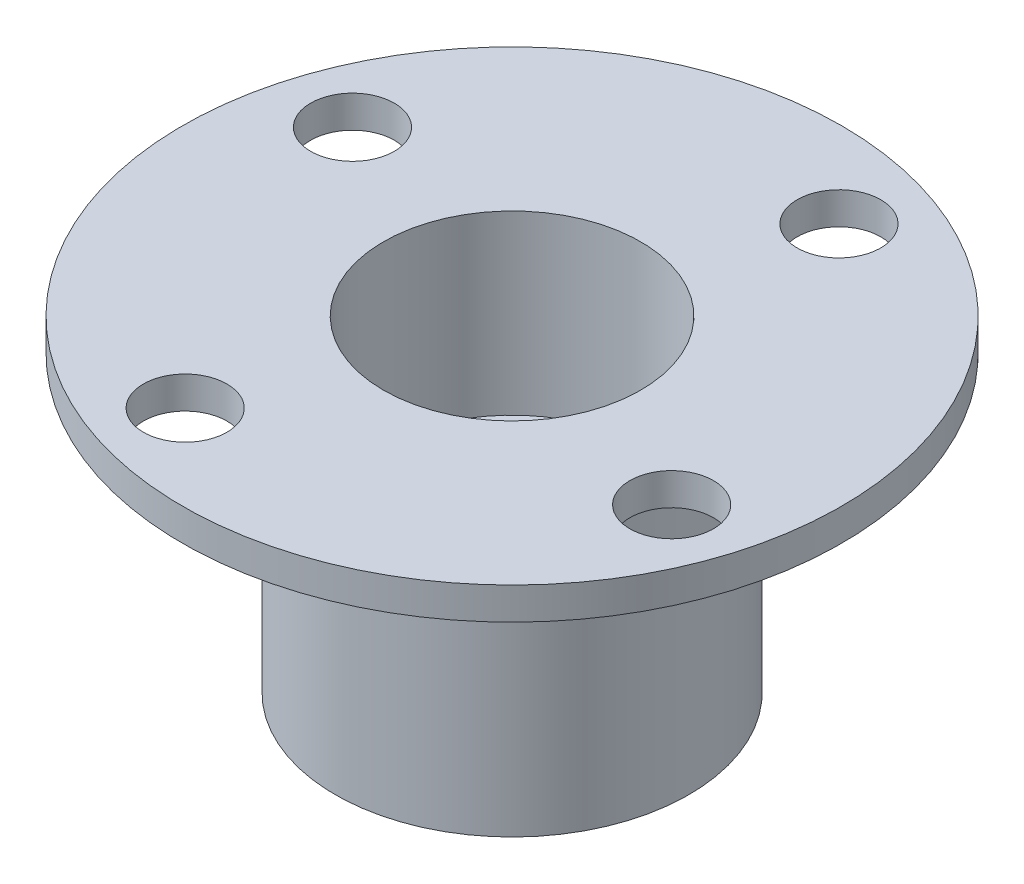
SolidWorks part; units mm, degrees
material "ABS"
ref_plane "Plan de face" through (0, 0, 0) normal (0, 0, 1) x (1, 0, 0)
ref_plane "Plan de dessus" through (0, 0, 0) normal (0, 1, 0) x (1, 0, 0)
ref_plane "Plan de droite" through (0, 0, 0) normal (1, 0, 0) x (0, 0, -1)
sketch "Esquisse1" plane through (0, -38.6013, 0) normal (0, -1, 0) x (1, 0, 0)
  circle A0 centre (14.0172, 17.25) radius 10.25
  arc A1 (9.5205, 8.039) -> (18.514, 26.461) centre (14.0172, 17.25) ccw construction
  dimension "D1" = 20.5
  dimension "D2" = 0
extrude "Boss.-Extru.1" add sketch "Esquisse1" along normal blind 1
hole_wizard "Dégagement M21" positions "Esquisse3" profile "Esquisse4" hole size "M2" standard "Ansi Metric" end condition up to next
sketch "Esquisse3" plane through (0, -39.6013, 0) normal (0, -1, 0) x (-1, 0, 0)
  circle A0 centre (-14.0172, -17.25) radius 8 construction
  point P0 (-11.4155, -24.8151)
  dimension "D1" = 16
sketch "Esquisse4" plane through (11.4155, -39.6013, 24.8151) normal (1, 0, 0) x (0, 0, -1)
  line L0 (0, 0) -> (0, 1.001)
  line L1 (0, 1.001) -> (1.3, 1.001)
  line L2 (1.3, 1.001) -> (1.3, 0)
  line L5 (1.3, 0) -> (0, 0)
  line L11 (0, -6.35) -> (0, 107.95) construction
  dimension "Diamètre du perçage jusqu'au prochain" = 2.6
  dimension "Profondeur du perçage jusqu'au prochain" = 1.001
pattern_circular "Répétition circulaire1" count 4 over 360 about axis through (14.0172, -39.6013, 17.25) along (0, -1, 0) of "Dégagement M21"
sketch "Esquisse9" plane through (0, -39.6013, 0) normal (0, -1, 0) x (-1, 0, 0)
  circle A0 centre (-14.0172, -17.25) radius 5.5
  dimension "D1" = 11
extrude "Boss.-Extru.4" add sketch "Esquisse9" along normal blind 9.146
sketch "Esquisse10" plane through (0, -48.7473, 0) normal (0, -1, 0) x (1, 0, 0)
  line L0 (11.9048, 19.85) -> (16.1297, 19.85)
  arc A0 (11.9048, 19.85) -> (16.1297, 19.85) centre (14.0172, 17.25) ccw
  dimension "D1" = 6.7
  dimension "D2" = 2.6
extrude "Enlèv. mat.-Extru.1" cut sketch "Esquisse10" against normal blind 4
fillet "Congé1" radius 0.5 1 edges at (14.0172, -39.6013, 11.75)
sketch "Esquisse11" plane through (0, -38.6013, 0) normal (0, 1, 0) x (1, 0, 0)
  circle A0 centre (14.0172, -17.25) radius 4
  circle A1 centre (14.0172, -17.25) radius 10.25 construction
  dimension "D1" = 8
extrude "Enlèv. mat.-Extru.2" cut sketch "Esquisse11" against normal blind 5.5
